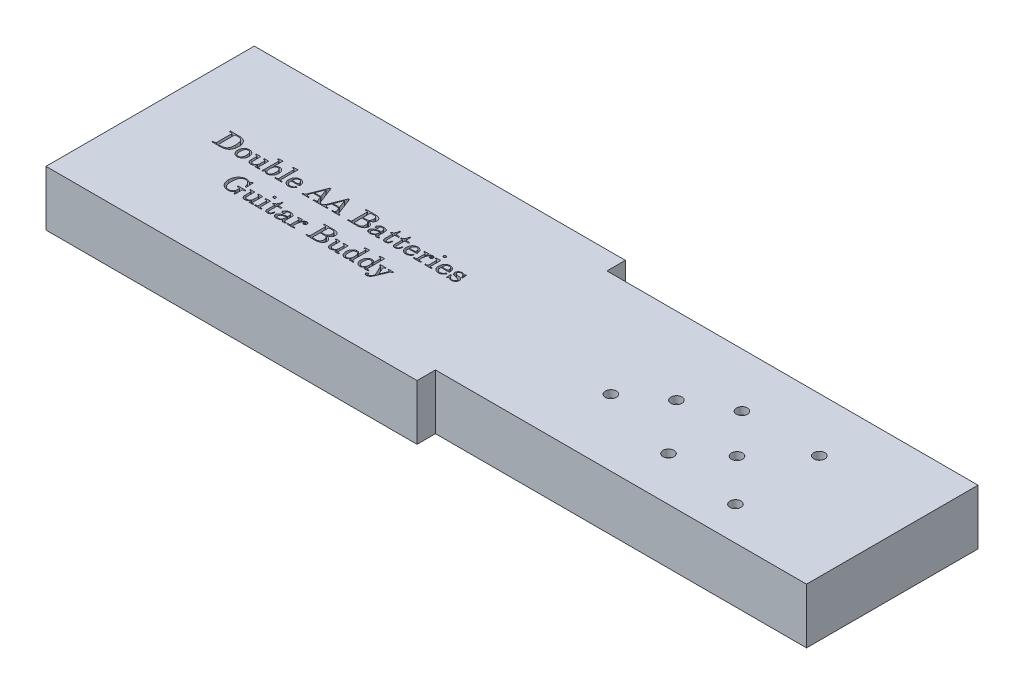
SolidWorks part; units mm, degrees
ref_plane "Front Plane" through (0, 0, 0) normal (0, 0, 1) x (1, 0, 0)
ref_plane "Top Plane" through (0, 0, 0) normal (0, 1, 0) x (1, 0, 0)
ref_plane "Right Plane" through (0, 0, 0) normal (1, 0, 0) x (0, 0, -1)
sketch "Sketch1" plane through (0, 0, 0) normal (0, 1, 0) x (1, 0, 0)
  line L0 (-60.0299, 41.2465) -> (67.9701, 41.2465)
  line L1 (-193.3799, 40.2465) -> (66.9701, 40.2465) construction
  line L2 (-193.3799, 40.2465) -> (-193.3799, -16.9035) construction
  line L3 (-193.3799, -16.9035) -> (66.9701, -16.9035) construction
  line L4 (66.9701, 40.2465) -> (66.9701, -16.9035) construction
  line L5 (67.9701, 41.2465) -> (67.9701, -17.9035)
  line L6 (-60.0299, -17.9035) -> (67.9701, -17.9035)
  line L8 (-60.0299, 41.2465) -> (-60.0299, 47.5965)
  line L9 (-60.0299, 47.5965) -> (-188.0299, 47.5965)
  line L10 (-188.0299, 47.5965) -> (-188.0299, -24.2535)
  line L11 (-188.0299, -24.2535) -> (-60.0299, -24.2535)
  line L12 (-60.0299, -24.2535) -> (-60.0299, -17.9035)
  line L13 (-194.3799, 41.2465) -> (67.9701, 41.2465) construction
  line L14 (-194.3799, -17.9035) -> (67.9701, -17.9035) construction
  line L15 (-194.3799, 41.2465) -> (-194.3799, -17.9035) construction
  dimension "D1" = 260.35
  dimension "D2" = 57.15
  dimension "D3" = 6.35
  dimension "D4" = 6.35
  dimension "D5" = 128
  dimension "D10" = 1
sketch "Sketch3" plane through (0, 0, 0) normal (0, 1, 0) x (1, 0, 0)
  line L1 (-70.1899, 40.2465) -> (66.9701, 40.2465) construction
  line L2 (-70.1899, 40.2465) -> (-70.1899, -16.9035) construction
  line L3 (-70.1899, -16.9035) -> (66.9701, -16.9035) construction
  line L4 (66.9701, 40.2465) -> (66.9701, -16.9035) construction
  line L5 (-62.5699, 24.1175) -> (-62.5699, -0.7745) construction
  line L7 (46.1421, 24.1175) -> (46.1421, -0.7745) construction
  circle A0 centre (-62.5699, 24.1175) radius 3.81
  circle A1 centre (-62.5699, -0.7745) radius 3.81
  circle A3 centre (46.1421, -0.7745) radius 3.81
  circle A4 centre (-62.5699, 24.1175) radius 1.5
  circle A5 centre (-62.5699, -0.7745) radius 1.5
  circle A6 centre (46.1421, 24.1175) radius 3.81
  circle A7 centre (46.1421, -0.7745) radius 1.5
  circle A8 centre (46.1421, 24.1175) radius 1.5
  point P9 (-62.5699, 11.6715)
  point P17 (-70.1899, 11.6715)
  point P18 (46.1421, 11.6715)
  point P19 (66.9701, 11.6715)
  dimension "D9" = 7.62
  dimension "D10" = 3
  dimension "D6" = 7.62
  dimension "D1" = 137.16
  dimension "D2" = 57.15
  dimension "D3" = 24.892
  dimension "D4" = 24.892
  dimension "D5" = 108.712
extrude "Boss-Extrude1" add sketch "Sketch1" against normal blind 19.05
sketch "Sketch4" plane through (0, -19.05, 0) normal (0, -1, 0) x (1, 0, 0)
  line L12 (-62.5699, -45.0565) -> (-62.5699, -38.7065)
  line L13 (-62.5699, -38.7065) -> (65.4301, -38.7065)
  line L14 (65.4301, -38.7065) -> (65.4301, 15.3635)
  line L15 (65.4301, 15.3635) -> (-62.5699, 15.3635)
  line L17 (-62.5699, -38.7065) -> (65.4301, -38.7065)
  line L18 (65.4301, -38.7065) -> (65.4301, 15.3635)
  line L19 (65.4301, 15.3635) -> (-62.5699, 15.3635)
  line L24 (-62.5699, -45.0565) -> (-62.5699, -38.7065)
  line L25 (-62.5699, 15.3635) -> (-62.5699, 21.7135)
  line L26 (-62.5699, 15.3635) -> (-62.5699, 21.7135)
  line L27 (-62.5699, 21.7135) -> (-185.4899, 21.7135)
  line L28 (-62.5699, 21.7135) -> (-185.4899, 21.7135)
  line L29 (-185.4899, 21.7135) -> (-185.4899, -45.0565)
  line L30 (-185.4899, 21.7135) -> (-185.4899, -45.0565)
  line L31 (-185.4899, -45.0565) -> (-62.5699, -45.0565)
  line L32 (-185.4899, -45.0565) -> (-62.5699, -45.0565)
  dimension "D1" = 2.54
extrude "Cut-Extrude1" cut sketch "Sketch4" against normal blind 16.51
extrude "Boss-Extrude3" add sketch "Sketch3" against normal blind 6.604
sketch "Sketch9" plane through (0, -2.54, 0) normal (0, -1, 0) x (1, 0, 0)
  line L3 (-142.3099, 6.7435) -> (-97.2199, -30.1165) construction
  line L4 (-188.0299, -47.5965) -> (-188.0299, 24.2535) construction
  line L5 (-169.7649, -38.1865) -> (-69.7649, -38.1865) construction
  line L6 (-169.7649, -38.1865) -> (-169.7649, 14.8135) construction
  line L7 (-169.7649, 14.8135) -> (-69.7649, 14.8135) construction
  line L8 (-69.7649, -38.1865) -> (-69.7649, 14.8135) construction
  line L9 (-169.7649, -38.1865) -> (-69.7649, 14.8135) construction
  line L10 (-169.7649, 14.8135) -> (-69.7649, -38.1865) construction
  circle A0 centre (-142.3099, 6.7435) radius 3.81
  circle A1 centre (-97.2199, -30.1165) radius 3.81
  circle A3 centre (-142.3099, 6.7435) radius 1.5
  circle A4 centre (-97.2199, -30.1165) radius 1.5
  point P8 (-119.7649, -11.6865)
  dimension "D4" = 7.62
  dimension "D5" = 3
  dimension "D1" = 36.86
  dimension "D2" = 45.09
  dimension "D3" = 45.72
  dimension "D6" = 53
  dimension "D7" = 100
extrude "Boss-Extrude5" add sketch "Sketch9" along normal blind 4.064
sketch "Sketch19" plane through (0, 0, 0) normal (0, 1, 0) x (1, 0, 0)
  line L1 (-49.2226, 24.1491) -> (59.4894, 24.1491) construction
  line L2 (-49.2226, 24.1491) -> (-49.2226, -0.7429) construction
  line L3 (-49.2226, -0.7429) -> (59.4894, -0.7429) construction
  line L4 (59.4894, 24.1491) -> (59.4894, -0.7429) construction
  line B0 (11.2883, -3.9487) -> (11.2883, 0.002)
  line B1 (8.7483, -1.4087) -> (-37.4738, -1.4087)
  line B2 (-37.4738, -1.4087) -> (-37.4738, -3.9487)
  line B3 (11.863, 6.9881) -> (11.863, 2.542)
  line B4 (14.403, 0.002) -> (14.403, 6.9881)
  line B5 (11.2883, 0.002) -> (14.403, 0.002)
  line B6 (14.403, 6.9881) -> (11.863, 6.9881)
  line B7 (11.863, 2.542) -> (8.7483, 2.542)
  line B8 (8.7483, 2.542) -> (8.7483, -1.4087)
  line B9 (-37.4738, -3.9487) -> (11.2883, -3.9487)
  line B10 (11.8153, -7.353) -> (49.9177, -7.353)
  line B11 (49.9177, -7.353) -> (49.9177, 30.6502)
  line B12 (49.9177, 30.6502) -> (37.3508, 30.6502)
  line B13 (37.3508, 30.6502) -> (37.3508, 28.1102)
  line B14 (37.3508, 28.1102) -> (47.3777, 28.1102)
  line B15 (47.3777, 28.1102) -> (47.3777, -4.813)
  line B16 (14.3553, -4.813) -> (47.3777, -4.813)
  line B17 (14.3553, -4.813) -> (14.3553, -0.3019)
  line B18 (14.3553, -0.3019) -> (11.8153, -0.3019)
  line B19 (11.8153, -0.3019) -> (11.8153, -4.813)
  line B20 (11.8153, -4.813) -> (-37.5739, -4.813)
  line B21 (-37.5739, -4.813) -> (-37.5739, -7.353)
  line B22 (-37.5739, -7.353) -> (11.8153, -7.353)
  line B23 (9.1683, 2.6444) -> (11.7083, 2.6444)
  line B24 (11.7083, 2.6444) -> (11.7083, 7.0378)
  line B25 (-23.7858, 6.6267) -> (-23.7858, 14.5312)
  line B26 (-21.2458, 14.5312) -> (-21.2458, 9.692)
  line B27 (-37.5046, 6.6267) -> (-23.7858, 6.6267)
  line B28 (-23.7858, 14.5312) -> (-21.2458, 14.5312)
  line B29 (9.1683, 7.0378) -> (9.1683, 6.564)
  line B30 (-37.5046, 4.024) -> (9.1683, 4.024)
  line B31 (9.1683, 6.564) -> (-21.2458, 6.564)
  line B32 (11.7083, 7.0378) -> (9.1683, 7.0378)
  line B33 (-21.2458, 6.564) -> (-21.2458, 9.692)
  line B34 (9.1683, 2.6444) -> (9.1683, 4.024)
  line B35 (-37.5046, 6.6267) -> (-37.5046, 4.024)
  line B36 (43.1962, -0.5831) -> (40.6562, -0.5831)
  line B37 (-37.7729, 22.4157) -> (-17.2303, 22.4157)
  line B38 (-17.2303, 22.4157) -> (-17.2303, 9.6802)
  line B39 (-17.2303, 9.6802) -> (43.1962, 9.6632)
  line B40 (-32.7209, 19.8757) -> (-19.7703, 19.8757)
  line B41 (-19.7703, 19.8757) -> (-19.7703, 7.1409)
  line B42 (-19.7703, 7.1409) -> (40.6562, 7.1239)
  line B43 (40.6562, 7.1239) -> (40.6562, -0.5831)
  line B44 (43.1962, 9.6632) -> (43.1962, -0.5831)
  line B45 (-37.7729, 19.8757) -> (-32.7209, 19.8757)
  line B46 (-37.7729, 22.4157) -> (-37.7729, 19.8757)
  line B47 (-37.8306, 22.7269) -> (-37.8306, 25.2669)
  line B48 (-37.8306, 25.2669) -> (-8.3007, 25.2669)
  line B49 (-8.3007, 25.2669) -> (-8.3007, 12.3957)
  line B50 (-8.3007, 12.3957) -> (8.1467, 12.3957)
  line B51 (10.6867, 9.8557) -> (-10.8407, 9.8557)
  line B52 (-10.8407, 9.8557) -> (-10.8407, 22.7269)
  line B53 (-10.8407, 22.7269) -> (-37.8306, 22.7269)
  line B54 (10.6867, 17.7995) -> (10.6867, 9.8557)
  line B55 (8.1467, 12.3957) -> (8.1467, 17.7995)
  line B56 (8.1467, 17.7995) -> (10.6867, 17.7995)
  line B57 (21.0302, 13.9828) -> (13.6406, 13.9828)
  line B58 (23.5702, 23.9763) -> (43.8489, 23.9763)
  line B59 (43.8489, 23.9763) -> (43.8489, 21.4363)
  line B60 (23.5702, 13.9828) -> (21.0302, 13.9828)
  line B61 (43.8489, 21.4363) -> (23.5702, 21.4363)
  line B62 (23.5702, 21.4363) -> (23.5702, 13.9828)
  line B63 (7.5356, 31.3187) -> (-38.125, 31.3187)
  line B64 (-38.125, 31.3187) -> (-38.125, 28.7787)
  line B65 (-38.125, 28.7787) -> (0.1437, 28.7787)
  line B66 (7.5356, 31.3187) -> (23.5702, 31.3187)
  line B67 (23.5702, 31.3187) -> (23.5702, 23.9763)
  line B68 (0.1437, 28.7787) -> (21.0302, 28.7787)
  line B69 (21.0302, 28.7787) -> (21.0302, 16.5228)
  line B70 (13.6406, 13.9828) -> (13.6406, 16.5228)
  line B71 (13.6406, 16.5228) -> (21.0302, 16.5228)
  line B72 (-38.0204, 28.4386) -> (-38.0204, 25.8986)
  line B73 (-38.0204, 25.8986) -> (-5.8865, 25.8986)
  line B74 (-5.8865, 25.8986) -> (3.6369, 25.8986)
  line B75 (3.6369, 25.8986) -> (3.6369, 21.4326)
  line B76 (6.1769, 28.4386) -> (-38.0204, 28.4386)
  line B77 (6.1769, 23.9726) -> (13.3555, 23.9726)
  line B78 (13.3555, 23.9726) -> (13.3555, 15.5018)
  line B79 (10.8294, 12.9618) -> (10.8294, 9.8553)
  line B80 (13.3694, 9.8553) -> (10.8294, 9.8553)
  line B81 (13.3694, 15.5018) -> (13.3694, 9.8553)
  line B82 (13.3555, 15.5018) -> (13.3694, 15.5018)
  line B83 (6.1769, 28.4386) -> (6.1769, 23.9726)
  line B84 (3.6369, 21.4326) -> (10.8155, 21.4326)
  line B85 (10.8155, 21.4326) -> (10.8155, 12.9618)
  line B86 (10.8155, 12.9618) -> (10.8294, 12.9618)
sketch_block_instance "Block2-2"
sketch_block "Block2" parameters "D1"=2.54, "D2"=2.54, "D3"=5.3633, "D4"=2.54
sketch_block_instance "Block3-2"
sketch_block "Block3" parameters "D1"=2.54, "D2"=2.54, "D3"=2.54, "D4"=2.54
sketch_block_instance "Block5-2"
sketch_block "Block5" parameters "D1"=2.54, "D2"=2.54, "D3"=8.9277, "D4"=32.9541
sketch_block_instance "Block6-2"
sketch_block "Block6" parameters "D1"=2.54, "D2"=2.54, "D3"=2.54, "D4"=2.54, "D5"=2.54
sketch_block_instance "Block9-2"
sketch_block "Block9" parameters "D1"=2.54, "D2"=2.54, "D3"=2.54, "D4"=2.8098
sketch_block_instance "Block10-2"
sketch_block "Block10" parameters "D1"=2.54, "D2"=2.54, "D3"=2.54, "D4"=2.54, "D5"=2.54
sketch_block_instance "Block11-2"
sketch_block "Block11" parameters "D1"=2.54, "D2"=2.54, "D3"=2.54, "D4"=2.54, "D5"=6.8507, "D6"=4.4659
sketch "Sketch11" plane through (0, 0, 0) normal (0, 1, 0) x (1, 0, 0)
  line L1 (-177.8699, 35.7855) -> (-76.2699, 35.7855) construction
  line L2 (-177.8699, 35.7855) -> (-177.8699, -12.4745) construction
  line L3 (-177.8699, -12.4745) -> (-76.2699, -12.4745) construction
  line L4 (-76.2699, 35.7855) -> (-76.2699, -12.4745) construction
  line L5 (67.9701, 41.2465) -> (-60.0299, 41.2465) construction
  line L6 (-188.0299, 47.5965) -> (-188.0299, -24.2535) construction
  dimension "D1" = 10.16
  dimension "D2" = 101.6
  dimension "D3" = 48.26
  dimension "D4" = 5.461
sketch "Sketch14" plane through (0, 0, 0) normal (0, 1, 0) x (1, 0, 0)
  circle A0 centre (31.8159, 22.6513) radius 1.905
  circle A1 centre (5.1334, 22.6513) radius 1.905
  circle A2 centre (-9.4341, 14.6251) radius 1.905
  circle A3 centre (-22.5378, 5.1052) radius 1.905
  circle A4 centre (5.1334, -2.6869) radius 1.905
  circle A5 centre (17.7069, 8.367) radius 1.905
  circle A6 centre (31.8159, -6.2678) radius 1.905
  point P14 (22.6309, 22.502)
  point P15 (5.1334, 22.502)
  point P16 (-9.5496, 12.3957)
  point P17 (-5.5957, 4.929)
  point P18 (8.7483, -1.4087)
  point P19 (10.0567, 0.6161)
  point P20 (16.942, -6.4205)
  point P21 (17.359, 8.6632)
  point P22 (21.6424, -6.164)
  point P23 (-22.3999, 5.4781)
  point P24 (16.942, 8.4094)
  point P25 (8.7483, 0.002)
  point P26 (8.7483, -2.3347)
  point P27 (-0.8148, 5.0188)
  point P28 (5.1334, 22.502)
  point P29 (22.6309, 8.3614)
  point P30 (13.1552, -6.2499)
  point P31 (17.092, 8.5132)
  point P32 (17.092, -6.5184)
  point P33 (0, 0)
  point P34 (22.2638, 29.6619)
  point P35 (22.2638, -6.2678)
  point P36 (0, 0)
  point P37 (36.811, 8.367)
  point P38 (-9.81, 20.8986)
  point P39 (-21.2458, 5.0369)
  point P40 (12.186, 20.8986)
  point P41 (0, 0)
  point P42 (31.8159, 22.6513)
  point P43 (17.7069, 8.367)
  point P44 (31.8159, -6.2678)
  point P45 (0, 0)
  point P46 (5.1334, 22.6513)
  point P47 (5.1334, -2.6869)
  point P48 (-9.4341, 14.6251)
  point P49 (-22.5378, 5.1052)
  dimension "D1" = 3.81
extrude "Cut-Extrude2" cut sketch "Sketch14" against normal blind 25.4
sketch "Sketch15" plane through (0, -19.05, 0) normal (0, -1, 0) x (1, 0, 0)
  line L0 (-60.0299, -47.5965) -> (-188.0299, -47.5965) construction
  line L1 (-188.0299, 24.2535) -> (-162.6299, 24.2535)
  line L2 (-188.0299, 24.2535) -> (-188.0299, -47.5965)
  line L3 (-188.0299, -47.5965) -> (-162.6299, -47.5965)
  line L4 (-162.6299, 24.2535) -> (-162.6299, -47.5965)
  dimension "D1" = 25.4
extrude "Boss-Extrude6" add sketch "Sketch15" against normal blind 2.54
sketch "Sketch16" plane through (-162.6299, 0, 0) normal (1, 0, 0) x (0, 0, -1)
  line L1 (-21.7135, -19.05) -> (45.1121, -19.05)
  line L2 (-21.7135, -19.05) -> (-21.7135, -13.97)
  line L3 (-21.7135, -13.97) -> (45.1121, -13.97)
  line L4 (45.1121, -19.05) -> (45.1121, -13.97)
  dimension "D1" = 5.08
extrude "Boss-Extrude7" add sketch "Sketch16" against normal blind 2.54
sketch "Sketch20" plane through (0, 0, 0) normal (0, 1, 0) x (1, 0, 0)
  line L0 (-188.0299, 11.6715) -> (-61.3058, 11.6715) construction
  line L1 (-188.0299, 47.5965) -> (-188.0299, -24.2535) construction
  text T0 "Double AA Batteries\r\nGuitar Buddy" font "Century Schoolbook" height in points 25
  point P1 (-124.6678, 11.6715)
extrude "Cut-Extrude4" cut sketch "Sketch20" against normal blind 2
